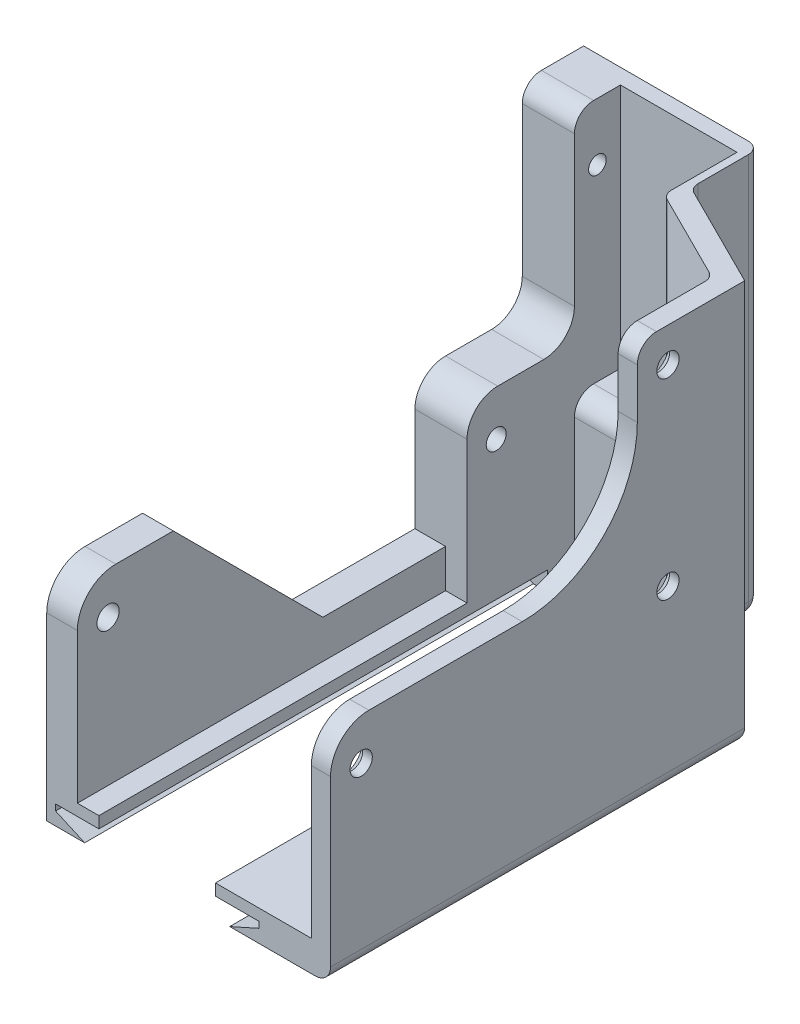
SolidWorks part; units mm, degrees
ref_plane "Спереди" through (0, 0, 0) normal (0, 0, 1) x (1, 0, 0)
ref_plane "Сверху" through (0, 0, 0) normal (0, 1, 0) x (1, 0, 0)
ref_plane "Справа" through (0, 0, 0) normal (1, 0, 0) x (0, 0, -1)
sketch "Эскиз1" plane through (0, 0, 0) normal (0, 1, 0) x (1, 0, 0)
  line L0 (0, 78.4998) -> (0, 0) construction
  line L1 (0, 0) -> (80.7208, 0) construction
sketch "Эскиз2" plane through (0, 0, 0) normal (0, 1, 0) x (1, 0, 0)
  line L0 (-16.9986, 152.8027) -> (29.0014, 152.8027)
  line L1 (29.0014, 152.8027) -> (29.0014, 134.8027)
  line L2 (29.0014, 134.8027) -> (57.0014, 120.8027)
  line L3 (57.0014, 120.8027) -> (57.0014, 12.8027)
  line L4 (57.0014, 12.8027) -> (27.0014, 12.8027)
  line L5 (27.0014, 12.8027) -> (27.0014, 148.8027)
  line L6 (27.0014, 148.8027) -> (-3.3986, 148.8027)
  line L7 (-3.3986, 148.8027) -> (-3.3986, 12.8027)
  line L8 (-3.3986, 12.8027) -> (-16.9986, 12.8027)
  line L9 (-16.9986, 12.8027) -> (-16.9986, 152.8027)
  dimension "D1" = 30.4
  dimension "D2" = 4
  dimension "D3" = 13.6
  dimension "D4" = 28
  dimension "D5" = 2
  dimension "D6" = 18
  dimension "D7" = 140
  dimension "D8" = 74
  dimension "D9" = 32
  dimension "D10" = 108
extrude "Бобышка-Вытянуть1" add sketch "Эскиз2" along normal blind 105
sketch "Эскиз3" plane through (0, 0, 0) normal (0, -1, 0) x (1, 0, 0)
  line L0 (27.0014, -148.8027) -> (27.0014, -12.8027) construction
  line L1 (-3.3986, -148.8027) -> (27.0014, -148.8027)
  line L2 (-3.3986, -148.8027) -> (-3.3986, -129.8027)
  line L3 (-3.3986, -129.8027) -> (27.0014, -129.8027)
  line L4 (27.0014, -148.8027) -> (27.0014, -129.8027)
  dimension "D1" = 19
extrude "Бобышка-Вытянуть2" add sketch "Эскиз3" against normal blind 3
sketch "Эскиз4" plane through (0, 3, 0) normal (0, 1, 0) x (1, 0, 0)
  line L0 (27.0014, 148.8027) -> (27.0014, 129.8027) construction
  line L1 (-3.3986, 148.8027) -> (27.0014, 148.8027)
  line L2 (-3.3986, 148.8027) -> (-3.3986, 136.8027)
  line L3 (-3.3986, 136.8027) -> (27.0014, 136.8027)
  line L4 (27.0014, 148.8027) -> (27.0014, 136.8027)
  dimension "D1" = 12
extrude "Бобышка-Вытянуть3" add sketch "Эскиз4" along normal blind 38
fillet "Скругление1" radius 5 1 edges at (11.8014, 41, -136.8027)
sketch "Эскиз5" plane through (0, 0, -12.8027) normal (0, 0, 1) x (1, 0, 0)
  line L0 (11.8014, 36) -> (11.8014, -10.7851) construction
  line L1 (27.0014, 36) -> (-3.3986, 36) construction
  line L2 (27.0014, -1.66) -> (27.0014, 5)
  line L3 (27.0014, 5) -> (38.3014, 5)
  line L4 (38.3014, 5) -> (38.3014, 3.4)
  line L5 (38.3014, 3.4) -> (27.0014, -1.66)
  line L6 (-14.6986, 5) -> (-14.6986, 3.4)
  line L7 (-3.3986, 5) -> (-14.6986, 5)
  line L8 (-3.3986, -1.66) -> (-3.3986, 5)
  line L9 (-14.6986, 3.4) -> (-3.3986, -1.66)
  line L10 (0, 0) -> (80.7208, 0) construction
  point P12 (-14.6986, 4.2)
  dimension "D1" = 53
  dimension "D2" = 1.6
  dimension "D3" = 6.66
  dimension "D4" = 5
  dimension "D5" = 11.3
  dimension "D6" = 15.2
extrude "Вырез-Вытянуть1" cut sketch "Эскиз5" against normal up to surface (117 mm away) up to face at (11.8014, 1.5, -129.8027)
sketch "Эскиз6" plane through (0, 105, 0) normal (0, 1, 0) x (1, 0, 0)
  line L0 (-16.9986, 12.8027) -> (52.0014, 12.8027)
  line L1 (27.0014, 12.8027) -> (57.0014, 12.8027) construction
  line L2 (52.0014, 12.8027) -> (52.0014, 117.3027)
  line L3 (52.0014, 117.3027) -> (27.0014, 129.8027)
  line L4 (27.0014, 129.8027) -> (27.0014, 108.8027)
  line L5 (27.0014, 148.8027) -> (27.0014, 12.8027) construction
  line L6 (27.0014, 108.8027) -> (-16.9986, 108.8027)
  line L7 (-16.9986, 152.8027) -> (-16.9986, 12.8027) construction
  line L8 (-16.9986, 108.8027) -> (-16.9986, 12.8027)
  line L9 (57.0014, 12.8027) -> (57.0014, 120.8027) construction
  line L10 (57.0014, 120.8027) -> (29.0014, 134.8027) construction
  line L11 (27.0014, 148.8027) -> (-3.3986, 148.8027) construction
  dimension "D1" = 5
  dimension "D2" = 40
extrude "Вырез-Вытянуть2" cut sketch "Эскиз6" against normal offset from surface (97 mm away) 3 up to face at (32.6514, 5, -71.3027)
sketch "Эскиз7" plane through (-16.9986, 0, 0) normal (-1, 0, 0) x (0, 0, 1)
  line L0 (-152.8027, 0) -> (-12.8027, 0) construction
  line L1 (-152.8027, 105) -> (-152.8027, 0) construction
  circle A0 centre (-116.4027, 41.2) radius 5
  dimension "D1" = 10
  dimension "D2" = 41.2
  dimension "D3" = 36.4
extrude "Вырез-Вытянуть3" cut sketch "Эскиз7" against normal blind 6.8
sketch "Эскиз8" plane through (-10.1986, 0, 0) normal (-1, 0, 0) x (0, 0, 1)
  circle A0 centre (-116.4027, 41.2) radius 2.6
  dimension "D1" = 5.2
extrude "Вырез-Вытянуть4" cut sketch "Эскиз8" against normal blind 20
chamfer "Фаска1" distance 3 angle 45 1 edges at (-10.1986, 41.2, -113.8027)
fillet "Скругление2" radius 3 4 edges at (52.0014, 56.5, -117.3027) (27.0014, 56.5, -129.8027) (29.0014, 52.5, -134.8027) (29.0014, 52.5, -152.8027)
sketch "Эскиз9" plane through (52.0014, 0, 0) normal (-1, 0, 0) x (0, 0, 1)
  line L0 (-100.8027, 125.7761) -> (-100.8027, 46) construction
  line L1 (-100.8027, 46) -> (-9.2893, 46) construction
  line L2 (-78.4998, 0) -> (0, 0) construction
  line L3 (-152.8027, 105) -> (-152.8027, 0) construction
  circle A0 centre (-100.8027, 46) radius 2.9
  circle A1 centre (-100.8027, 96) radius 2.9
  circle A2 centre (-20.8027, 46) radius 2.9
  dimension "D1" = 5.8
  dimension "D2" = 80
  dimension "D3" = 50
  dimension "D4" = 46
  dimension "D5" = 52
extrude "Вырез-Вытянуть5" cut sketch "Эскиз9" against normal through all
sketch "Эскиз10" plane through (52.0014, 0, 0) normal (-1, 0, 0) x (0, 0, 1)
  line L0 (-152.8027, 105) -> (-152.8027, 0) construction
  line L1 (-12.8027, 105) -> (-92.8027, 105)
  line L2 (-12.8027, 105) -> (-12.8027, 57)
  line L3 (-12.8027, 57) -> (-92.8027, 57)
  line L4 (-92.8027, 105) -> (-92.8027, 57)
  dimension "D1" = 48
  dimension "D2" = 60
extrude "Вырез-Вытянуть6" cut sketch "Эскиз10" against normal blind 20
fillet "Скругление3" radius 30 1 edges at (54.5014, 57, -92.8027)
sketch "Эскиз11" plane through (-16.9986, 0, 0) normal (-1, 0, 0) x (0, 0, 1)
  line L0 (-152.8027, 105) -> (-152.8027, 0) construction
  line L1 (-108.8027, 105) -> (-136.8027, 105)
  line L2 (-108.8027, 105) -> (-108.8027, 53)
  line L3 (-108.8027, 53) -> (-136.8027, 53)
  line L4 (-136.8027, 105) -> (-136.8027, 53)
  dimension "D1" = 16
  dimension "D2" = 52
extrude "Вырез-Вытянуть7" cut sketch "Эскиз11" against normal blind 20
fillet "Скругление4" radius 8 2 edges at (-10.1986, 53, -136.8027) (-10.1986, 53, -108.8027)
sketch "Эскиз12" plane through (0, 8, 0) normal (0, 1, 0) x (1, 0, 0)
  line L0 (26.0014, 152.8027) -> (-16.9986, 152.8027) construction
  line L1 (-16.9986, 12.8027) -> (-8.9986, 12.8027)
  line L2 (-16.9986, 12.8027) -> (-16.9986, 36.8027)
  line L3 (-16.9986, 36.8027) -> (-8.9986, 36.8027)
  line L4 (-8.9986, 12.8027) -> (-8.9986, 36.8027)
  dimension "D1" = 8
  dimension "D2" = 116
extrude "Бобышка-Вытянуть4" add sketch "Эскиз12" along normal up to surface (49 mm away) up to face at (54.5014, 57, -37.8027)
chamfer "Фаска2" distance 50 angle 45 1 edges at (-12.9986, 8, -36.8027)
fillet "Скругление5" radius 10 2 edges at (54.5014, 57, -12.8027) (-12.9986, 57, -12.8027)
sketch "Эскиз13" plane through (57.0014, 0, 0) normal (1, 0, 0) x (0, 0, -1)
  circle A0 centre (20.8027, 46) radius 2.9
extrude "Вырез-Вытянуть8" cut sketch "Эскиз13" against normal through all
chamfer "Фаска3" distance 2.5 angle 45 4 edges at (52.0014, 96, -97.9027) (52.0014, 46, -17.9027) (52.0014, 46, -97.9027) (-16.9986, 46, -23.7027)
sketch "Эскиз14" plane through (-16.9986, 0, 0) normal (-1, 0, 0) x (0, 0, 1)
  line L0 (-142.8027, 122.3898) -> (-142.8027, -15.2177) construction
  line L1 (-152.8027, 105) -> (-152.8027, 0) construction
  line L2 (-152.8027, 0) -> (-12.8027, 0) construction
  circle A0 centre (-142.8027, 90) radius 2.3
  circle A1 centre (-142.8027, 30) radius 2.3
  dimension "D2" = 4.6
  dimension "D3" = 60
  dimension "D4" = 30
  dimension "D1" = 10
extrude "Вырез-Вытянуть9" cut sketch "Эскиз14" against normal blind 15
fillet "Скругление6" radius 5 2 edges at (54.5014, 105, -92.8027) (-10.1986, 105, -136.8027)
fillet "Скругление7" radius 0.8 3 edges at (-16.9986, 41.2, -111.4027) (-16.9986, 30, -140.5027) (-16.9986, 90, -140.5027)
fillet "Скругление8" radius 4 6 edges at (43.8306, 0, -127.3881) (29.4495, 0, -135.0796) (4.5014, 0, -152.8027) (28.1228, 0, -151.924) (29.0014, 0, -143.2298) (57.0014, 0, -66.8027)
sketch "Эскиз15" plane through (0, 8, 0) normal (0, 1, 0) x (1, 0, 0)
  line L0 (-8.9986, 12.8027) -> (-8.9986, 86.8027) construction
  line L1 (-16.9986, 108.8027) -> (-8.9986, 108.8027)
  line L2 (-16.9986, 108.8027) -> (-16.9986, 68.3299)
  line L3 (-16.9986, 68.3299) -> (-8.9986, 68.3299)
  line L4 (-8.9986, 108.8027) -> (-8.9986, 68.3299)
extrude "Бобышка-Вытянуть5" add sketch "Эскиз15" along normal blind 10
